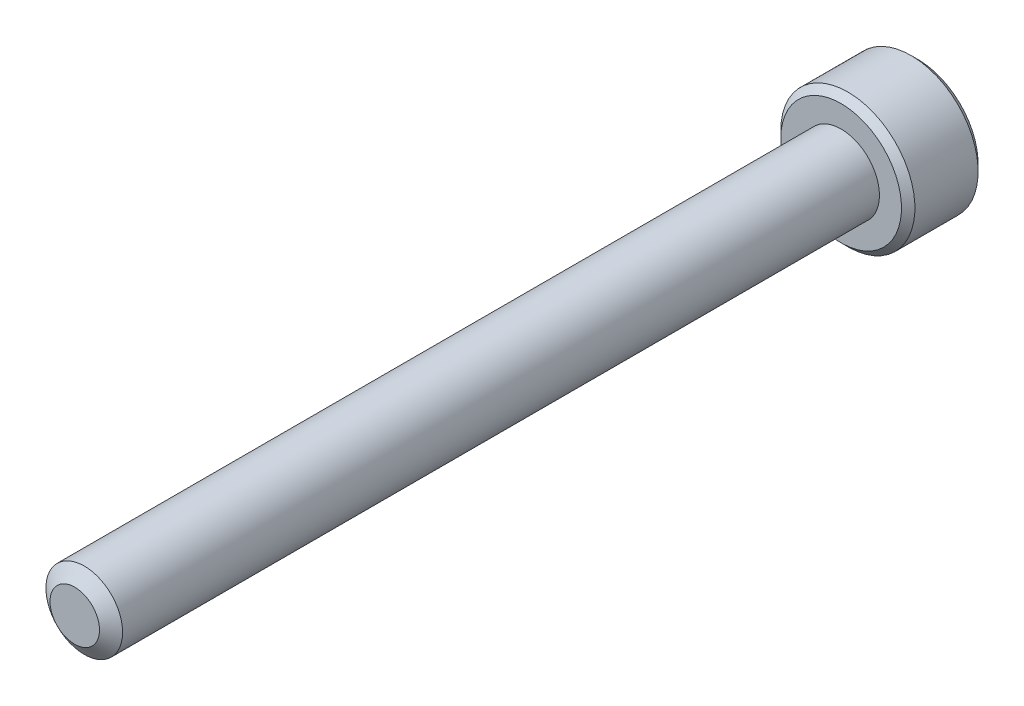
SolidWorks part; units mm, degrees
other "DetailItem1"
material "1.4310 (X10CrNi18-8)"
ref_plane "Front Plane" through (0, 0, 0) normal (0, 0, 1) x (1, 0, 0)
ref_plane "Top Plane" through (0, 0, 0) normal (0, 1, 0) x (1, 0, 0)
ref_plane "Right Plane" through (0, 0, 0) normal (1, 0, 0) x (0, 0, -1)
sketch "Sketch1" plane through (0, 0, 0) normal (0, 0, 1) x (1, 0, 0)
  circle A0 centre (0, 0) radius 2
  dimension "OD" = 4
extrude "Extrude1" add sketch "Sketch1" against normal blind 40
sketch "Sketch2" plane through (0, 0, 0) normal (0, 0, 1) x (1, 0, 0)
  circle A0 centre (0, 0) radius 2 construction
  circle A1 centre (0, 0) radius 2
curve "Helix/Spiral1" pitch 0.7 height 40.7 turns 58.1429 parameters "pitch"=0.7
sketch "Sketch3" plane through (0, 0, 0) normal (1, 0, 0) x (0, 0, -1)
  line L0 (-0.6125, 2) -> (-0.35, 1.5453)
  line L1 (-0.35, 1.5453) -> (-0.2625, 1.5453)
  line L2 (-0.2625, 1.5453) -> (0, 2)
  line L3 (-0.6125, 2) -> (0, 2)
  line L4 (-0.3062, 2) -> (-0.3062, 1.5453) construction
  line L5 (-0.4812, 1.7727) -> (-0.1312, 1.7727) construction
  line L6 (0, 2) -> (0, -2) construction
  dimension "D1" = 0.0875
  dimension "D2" = 0.35
  dimension "D3" = 60
sweep "Cut-Sweep1" [suppressed] cut profiles "Sketch3" path "Helix/Spiral1"
sketch "Sketch4" plane through (0, 0, 0) normal (1, 0, 0) x (0, 0, -1)
  line L0 (0.4962, 2) -> (0, 1.2913)
  line L1 (0, 1.2913) -> (0, 2)
  line L2 (0.4962, 2) -> (0, 2)
  line L3 (-0.6125, 2) -> (0, 2) construction
  line L4 (0, 0) -> (7.0209, 0) construction
  dimension "D1" = 55
  dimension "D2" = 0.254
revolve "Cut-Revolve1" cut sketch "Sketch4" angle 360 about L4
sketch "Sketch6" plane through (0, 0, -40) normal (0, 0, -1) x (-1, 0, 0)
  circle A0 centre (0, 0) radius 3.5
  dimension "head dia" = 7
extrude "Extrude2" add sketch "Sketch6" along normal blind 4
sketch "Sketch7" plane through (0, 0, -44) normal (0, 0, -1) x (-1, 0, 0)
  line L1 (0, 1.7321) -> (-1.5, 0.866)
  line L2 (-1.5, 0.866) -> (-1.5, -0.866)
  line L3 (-1.5, -0.866) -> (0, -1.7321)
  line L4 (0, -1.7321) -> (1.5, -0.866)
  line L5 (1.5, -0.866) -> (1.5, 0.866)
  line L6 (1.5, 0.866) -> (0, 1.7321)
  circle A0 centre (0, 0) radius 1.5 construction
  dimension "hex dia" = 3
extrude "Cut-Extrude1" cut sketch "Sketch7" against normal blind 2.25
sketch "Sketch8" plane through (0, 0, -44) normal (0, 0, -1) x (-1, 0, 0)
  circle A0 centre (0, 0) radius 1.7321
extrude "Cut-Extrude2" cut sketch "Sketch8" against normal through all draft 45
chamfer "Chamfer1" distance 0.35 angle 45 2 edges at (-3.5, 0, -44) (-3.5, 0, -40)
sketch "Sketch10" plane through (0, 0, -40) normal (0, 0, 1) x (1, 0, 0)
  circle A1 centre (0, 0) radius 2
  circle A2 centre (0, 0) radius 2
  dimension "D1" = 0
ref_plane "Plane1" through (0, 0, 0) normal (0, 0, 1) x (1, 0, 0)
extrude "partial thread" [suppressed] add sketch "Sketch10" along normal up to surface (10 mm away) separate body up to plane "Plane1"
chamfer "Chamfer2" [suppressed] distance 0.08 angle 45
combine bodies "Combine1" [suppressed] operation type add bodies to combine 107 108
sketch "Sketch9" plane through (0, 0, 0) normal (1, 0, 0) x (0, 0, -1)
  line L0 (0, 2) -> (0, -2) construction
  line L1 (1.75, 2) -> (1.75, -2) construction
  dimension "D1" = 1.75
equation "\"D3@Helix/Spiral1\" = \"screw length@Extrude1\"+\"pitch@Helix/Spiral1\""
equation "\"D1@Sketch3\" = \"pitch@Helix/Spiral1\"*.125"
equation "\"D2@Sketch3\" = \"pitch@Helix/Spiral1\"*.5"
equation "\"D1@Cut-Extrude1\" = \"hex dia@Sketch7\"*.75"
equation "\"D1@Chamfer1\" = \"head dia@Sketch6\"*.05"
equation "\"D1@Sketch9\" = \"pitch@Helix/Spiral1\"*2.5"
equation "\"D1@Chamfer2\"=\"OD@Sketch1\"*.02"
